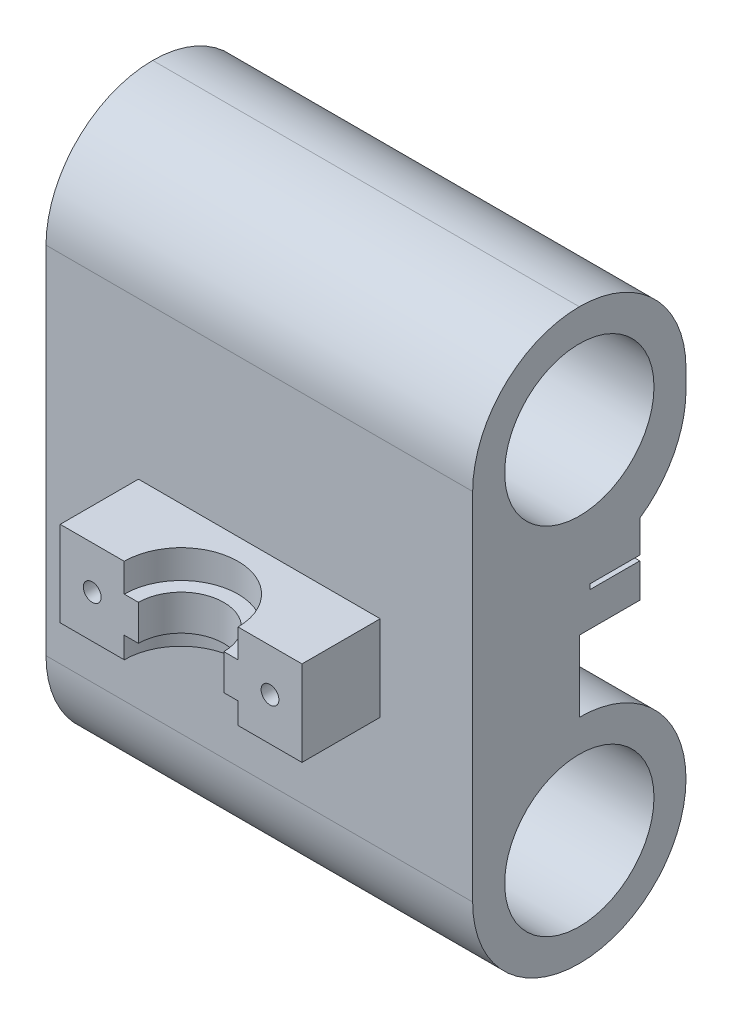
SolidWorks part; units mm, degrees
ref_plane "Спереди" through (0, 0, 0) normal (0, 0, 1) x (1, 0, 0)
ref_plane "Сверху" through (0, 0, 0) normal (0, 1, 0) x (1, 0, 0)
ref_plane "Справа" through (0, 0, 0) normal (1, 0, 0) x (0, 0, -1)
sketch "Эскиз1" plane through (0, 0, 0) normal (1, 0, 0) x (0, 0, -1)
  line L0 (0, 0) -> (0, 80)
  line L1 (0, 80) -> (30, 80)
  line L2 (30, 80) -> (30, 50)
  line L3 (16.5, 40) -> (15, 40)
  line L4 (15, 40) -> (15, 30)
  line L5 (15, 30) -> (30, 30)
  line L6 (30, 30) -> (30, 0)
  line L7 (30, 0) -> (0, 0)
  line L8 (15, 65) -> (15, 15) construction
  line L9 (16.5, 44.8) -> (23.5, 44.8)
  line L10 (23.5, 44.8) -> (23.5, 40)
  line L11 (16.5, 45.5) -> (23.5, 45.5)
  line L12 (16.5, 45.5) -> (16.5, 44.8)
  line L13 (30, 50) -> (23.5, 50)
  line L14 (23.5, 50) -> (23.5, 45.5)
  line L15 (23.5, 40) -> (16.5, 40)
  circle A0 centre (15, 15) radius 10.5
  circle A1 centre (15, 65) radius 10.5
  point P13 (0, 40)
  dimension "D4" = 21
  dimension "D6" = 21
  dimension "D2" = 15
  dimension "D3" = 15
  dimension "D5" = 30
  dimension "D7" = 15
  dimension "D8" = 50
  dimension "D9" = 15
  dimension "D10" = 1.5
  dimension "D11" = 0.7
  dimension "D12" = 8.5
  dimension "D13" = 15
  dimension "D14" = 19.5
  dimension "D15" = 8.5
  dimension "D16" = 15
extrude "Бобышка-Вытянуть2" add sketch "Эскиз1" along normal blind 60
fillet "Скругление1" radius 15 1 edges at (30, 30, -30)
fillet "Скругление5" radius 15 1 edges at (30, 80, -30)
fillet "Скругление3" radius 15 1 edges at (30, 0, -30)
sketch "Эскиз2" plane through (0, 0, 0) normal (0, 0, 1) x (1, 0, 0)
  line L0 (13, 31) -> (13, 43)
  line L2 (13, 43) -> (47, 43)
  line L3 (47, 43) -> (47, 31)
  line L4 (47, 31) -> (13, 31)
  line L5 (60, 0) -> (0, 0) construction
  point P4 (30, 31)
  point P7 (30, 0)
  dimension "D1" = 31
  dimension "D2" = 12
  dimension "D3" = 34
extrude "Бобышка-Вытянуть3" add sketch "Эскиз2" along normal blind 11
sketch "Эскиз3" plane through (0, 43, 0) normal (0, 1, 0) x (1, 0, 0)
  line L0 (47, -11) -> (13, -11) construction
  line L1 (24, -11) -> (36, -11)
  line L2 (36, -11) -> (36.0417, -10.8799)
  arc A0 (36, -11) -> (24, -11) centre (30, -11) ccw
  line M3 (13, -11) -> (47, -11)
  dimension "D1" = 12
extrude "Вырез-Вытянуть1" cut sketch "Эскиз3" against normal up to surface (12 mm away) contours A0 M3 region at (30, 43, 8.4535) up to face at (30, 31, 5.5)
sketch "Эскиз4" plane through (0, 43, 0) normal (0, 1, 0) x (1, 0, 0)
  line L0 (47, -11) -> (36, -11) construction
  line L1 (24, -11) -> (13, -11) construction
  arc A0 (38, -11) -> (22, -11) centre (30, -11) ccw
  arc A1 (36, -11) -> (24, -11) centre (30, -11) ccw construction
  point P11 (30, -5)
  dimension "D1" = 16
extrude "Вырез-Вытянуть2" cut sketch "Эскиз4" against normal blind 4 and the other way through all
sketch "Эскиз5" plane through (0, 31, 0) normal (0, -1, 0) x (-1, 0, 0)
  line L0 (-13, -11) -> (-24, -11) construction
  line L1 (-36, -11) -> (-47, -11) construction
  arc A0 (-22, -11) -> (-38, -11) centre (-30, -11) ccw
  arc A1 (-24, -11) -> (-36, -11) centre (-30, -11) ccw construction
  point P11 (-30, -5)
  dimension "D1" = 16
extrude "Вырез-Вытянуть3" cut sketch "Эскиз5" against normal blind 3 and the other way through all
sketch "Эскиз6" plane through (0, 0, 11) normal (0, 0, 1) x (1, 0, 0)
  line L0 (13, 43) -> (13, 31) construction
  line L1 (47, 31) -> (47, 43) construction
  line L2 (47, 37) -> (12.8652, 37) construction
  circle A0 centre (17.5, 37) radius 1.25
  circle A1 centre (42.5, 37) radius 1.25
  dimension "D1" = 2.5
  dimension "D2" = 2.5
  dimension "D3" = 4.5
  dimension "D4" = 4.5
extrude "Вырез-Вытянуть4" cut sketch "Эскиз6" against normal up to vertex (11 mm away) up to point (13, 31, 0)
fillet "Скругление10" radius 15 1 edges at (30, 80, 0)
fillet "Скругление11" radius 15 1 edges at (30, 0, 0)
fillet "Скругление13" radius 15 1 edges at (30, 50, -30)
sketch "Эскиз9" plane through (0, 0, -23.5) normal (0, 0, -1) x (-1, 0, 0)
  line L0 (-59.15, 44.8) -> (-59.15, 43.9)
  line L1 (-60, 44.8) -> (0, 44.8) construction
  line L2 (-59.15, 43.9) -> (-58.05, 43.9)
  line L3 (-58.05, 43.9) -> (-58.05, 44.8)
  line L4 (-58.05, 44.8) -> (-59.15, 44.8)
  line L5 (-60, 40) -> (-60, 44.8) construction
  line L6 (-56.1, 44.8) -> (-57.2, 44.8)
  line L7 (-56.1, 43.9) -> (-56.1, 44.8)
  line L8 (-57.2, 43.9) -> (-56.1, 43.9)
  line L9 (-57.2, 44.8) -> (-57.2, 43.9)
  line L10 (-54.15, 44.8) -> (-55.25, 44.8)
  line L11 (-54.15, 43.9) -> (-54.15, 44.8)
  line L12 (-55.25, 43.9) -> (-54.15, 43.9)
  line L13 (-55.25, 44.8) -> (-55.25, 43.9)
  line L14 (-52.2, 44.8) -> (-53.3, 44.8)
  line L15 (-52.2, 43.9) -> (-52.2, 44.8)
  line L16 (-53.3, 43.9) -> (-52.2, 43.9)
  line L17 (-53.3, 44.8) -> (-53.3, 43.9)
  line L18 (-50.25, 44.8) -> (-51.35, 44.8)
  line L19 (-50.25, 43.9) -> (-50.25, 44.8)
  line L20 (-51.35, 43.9) -> (-50.25, 43.9)
  line L21 (-51.35, 44.8) -> (-51.35, 43.9)
  line L22 (-48.3, 44.8) -> (-49.4, 44.8)
  line L23 (-48.3, 43.9) -> (-48.3, 44.8)
  line L24 (-49.4, 43.9) -> (-48.3, 43.9)
  line L25 (-49.4, 44.8) -> (-49.4, 43.9)
  line L26 (-46.35, 44.8) -> (-47.45, 44.8)
  line L27 (-46.35, 43.9) -> (-46.35, 44.8)
  line L28 (-47.45, 43.9) -> (-46.35, 43.9)
  line L29 (-47.45, 44.8) -> (-47.45, 43.9)
  line L30 (-44.4, 44.8) -> (-45.5, 44.8)
  line L31 (-44.4, 43.9) -> (-44.4, 44.8)
  line L32 (-45.5, 43.9) -> (-44.4, 43.9)
  line L33 (-45.5, 44.8) -> (-45.5, 43.9)
  line L34 (-42.45, 44.8) -> (-43.55, 44.8)
  line L35 (-42.45, 43.9) -> (-42.45, 44.8)
  line L36 (-43.55, 43.9) -> (-42.45, 43.9)
  line L37 (-43.55, 44.8) -> (-43.55, 43.9)
  line L38 (-40.5, 44.8) -> (-41.6, 44.8)
  line L39 (-40.5, 43.9) -> (-40.5, 44.8)
  line L40 (-41.6, 43.9) -> (-40.5, 43.9)
  line L41 (-41.6, 44.8) -> (-41.6, 43.9)
  line L42 (-38.55, 44.8) -> (-39.65, 44.8)
  line L43 (-38.55, 43.9) -> (-38.55, 44.8)
  line L44 (-39.65, 43.9) -> (-38.55, 43.9)
  line L45 (-39.65, 44.8) -> (-39.65, 43.9)
  line L46 (-36.6, 44.8) -> (-37.7, 44.8)
  line L47 (-36.6, 43.9) -> (-36.6, 44.8)
  line L48 (-37.7, 43.9) -> (-36.6, 43.9)
  line L49 (-37.7, 44.8) -> (-37.7, 43.9)
  dimension "D1" = 1.1
  dimension "D2" = 0.9
  dimension "D3" = 0.85
  dimension "D4" = 12
extrude "Вырез-Вытянуть6" cut sketch "Эскиз9" against normal up to surface (7 mm away) up to face at (30, 45.15, -16.5)
sketch "Эскиз11" plane through (0, 0, -23.5) normal (0, 0, -1) x (-1, 0, 0)
  line L0 (-0.85, 44.8) -> (-0.85, 43.9)
  line L1 (-36.6, 44.8) -> (0, 44.8) construction
  line L2 (-0.85, 43.9) -> (-1.95, 43.9)
  line L3 (-1.95, 43.9) -> (-1.95, 44.8)
  line L4 (-1.95, 44.8) -> (-0.85, 44.8)
  line L5 (0, 40) -> (0, 44.8) construction
  line L6 (-3.9, 44.8) -> (-2.8, 44.8)
  line L7 (-3.9, 43.9) -> (-3.9, 44.8)
  line L8 (-2.8, 43.9) -> (-3.9, 43.9)
  line L9 (-2.8, 44.8) -> (-2.8, 43.9)
  line L10 (-5.85, 44.8) -> (-4.75, 44.8)
  line L11 (-5.85, 43.9) -> (-5.85, 44.8)
  line L12 (-4.75, 43.9) -> (-5.85, 43.9)
  line L13 (-4.75, 44.8) -> (-4.75, 43.9)
  line L14 (-7.8, 44.8) -> (-6.7, 44.8)
  line L15 (-7.8, 43.9) -> (-7.8, 44.8)
  line L16 (-6.7, 43.9) -> (-7.8, 43.9)
  line L17 (-6.7, 44.8) -> (-6.7, 43.9)
  line L18 (-9.75, 44.8) -> (-8.65, 44.8)
  line L19 (-9.75, 43.9) -> (-9.75, 44.8)
  line L20 (-8.65, 43.9) -> (-9.75, 43.9)
  line L21 (-8.65, 44.8) -> (-8.65, 43.9)
  line L22 (-11.7, 44.8) -> (-10.6, 44.8)
  line L23 (-11.7, 43.9) -> (-11.7, 44.8)
  line L24 (-10.6, 43.9) -> (-11.7, 43.9)
  line L25 (-10.6, 44.8) -> (-10.6, 43.9)
  line L26 (-13.65, 44.8) -> (-12.55, 44.8)
  line L27 (-13.65, 43.9) -> (-13.65, 44.8)
  line L28 (-12.55, 43.9) -> (-13.65, 43.9)
  line L29 (-12.55, 44.8) -> (-12.55, 43.9)
  line L30 (-15.6, 44.8) -> (-14.5, 44.8)
  line L31 (-15.6, 43.9) -> (-15.6, 44.8)
  line L32 (-14.5, 43.9) -> (-15.6, 43.9)
  line L33 (-14.5, 44.8) -> (-14.5, 43.9)
  line L34 (-17.55, 44.8) -> (-16.45, 44.8)
  line L35 (-17.55, 43.9) -> (-17.55, 44.8)
  line L36 (-16.45, 43.9) -> (-17.55, 43.9)
  line L37 (-16.45, 44.8) -> (-16.45, 43.9)
  line L38 (-19.5, 44.8) -> (-18.4, 44.8)
  line L39 (-19.5, 43.9) -> (-19.5, 44.8)
  line L40 (-18.4, 43.9) -> (-19.5, 43.9)
  line L41 (-18.4, 44.8) -> (-18.4, 43.9)
  line L42 (-21.45, 44.8) -> (-20.35, 44.8)
  line L43 (-21.45, 43.9) -> (-21.45, 44.8)
  line L44 (-20.35, 43.9) -> (-21.45, 43.9)
  line L45 (-20.35, 44.8) -> (-20.35, 43.9)
  line L46 (-23.4, 44.8) -> (-22.3, 44.8)
  line L47 (-23.4, 43.9) -> (-23.4, 44.8)
  line L48 (-22.3, 43.9) -> (-23.4, 43.9)
  line L49 (-22.3, 44.8) -> (-22.3, 43.9)
  dimension "D1" = 0.85
  dimension "D2" = 1.1
  dimension "D3" = 0.9
  dimension "D4" = 12
extrude "Вырез-Вытянуть7" cut sketch "Эскиз11" against normal up to surface (7 mm away) up to face at (46.5, 44.4115, -16.5)
